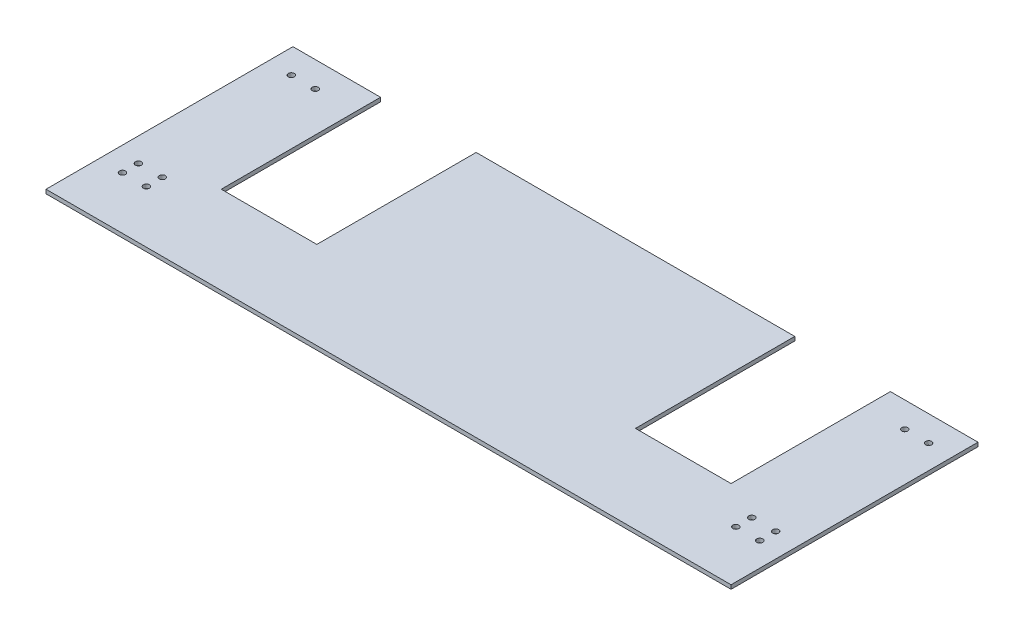
SolidWorks part; units mm, degrees
ref_plane "Front Plane" through (0, 0, 0) normal (0, 0, 1) x (1, 0, 0)
ref_plane "Top Plane" through (0, 0, 0) normal (0, 1, 0) x (1, 0, 0)
ref_plane "Right Plane" through (0, 0, 0) normal (1, 0, 0) x (0, 0, -1)
sketch "Sketch1" plane through (0, 0, 0) normal (0, 0, 1) x (1, 0, 0)
  line L1 (-273.05, -1.5875) -> (273.05, -1.5875)
  line L2 (-273.05, -1.5875) -> (-273.05, 1.5875)
  line L3 (-273.05, 1.5875) -> (273.05, 1.5875)
  line L4 (273.05, -1.5875) -> (273.05, 1.5875)
  line L5 (-273.05, -1.5875) -> (273.05, 1.5875) construction
  line L6 (-273.05, 1.5875) -> (273.05, -1.5875) construction
  point P0 (0, 0)
  dimension "D1" = 3.175
  dimension "D2" = 546.1
extrude "Boss-Extrude1" add sketch "Sketch1" along normal blind 184.15
sketch "Sketch2" plane through (0, 1.5875, 0) normal (0, 1, 0) x (1, 0, 0)
  line L4 (273.05, 0) -> (-273.05, 0) construction
  line L5 (-273.05, -184.15) -> (-273.05, 0) construction
  line L6 (0, 0) -> (0, -184.15)
  line L7 (273.05, -184.15) -> (-273.05, -184.15) construction
  line L11 (-273.05, -68.58) -> (273.05, -68.58)
  line L15 (273.05, -184.15) -> (273.05, 0) construction
  line L19 (-254, -129.54) -> (-251.587, -129.54) construction
  line L20 (-254, -129.54) -> (-254, -127.762)
  line L21 (-254, -127.762) -> (-254, -129.54)
  line L22 (-255.778, -129.54) -> (-254, -129.54)
  line L23 (-254, -131.318) -> (-254, -129.54)
  line L24 (-254, -129.54) -> (-254, -131.318)
  line L34 (-232.537, -129.54) -> (254, -129.54)
  circle A18 centre (-234.95, -129.54) radius 2.413
  circle A20 centre (-254, -129.54) radius 2.413
  circle A27 centre (-254, -7.62) radius 2.413
  circle A28 centre (-234.95, -7.62) radius 2.413
  circle A29 centre (254, -7.62) radius 2.413
  circle A30 centre (234.95, -7.62) radius 2.413
  circle A31 centre (254, -129.54) radius 2.413
  circle A32 centre (234.95, -129.54) radius 2.413
  dimension "D2" = 4.826
  dimension "D5" = 68.58
  dimension "D13" = 19.05
  dimension "D14" = 4.826
  dimension "D17" = 19.05
extrude "Cut-Extrude2" cut sketch "Sketch2" against normal through all contours A27 | A28 | A31 | A29 | A18 | A20 | A32 | A30 region at (254, 1.5875, 127.1952) region at (-254, 1.5875, 7.62) region at (-234.95, 1.5875, 7.62)
sketch "Sketch3" plane through (0, 1.5875, 0) normal (0, 1, 0) x (1, 0, 0)
  line L0 (-273.05, -184.15) -> (-273.05, 0) construction
  line L1 (-273.05, -42.9615) -> (273.05, -42.9615)
  line L2 (-273.05, -42.9615) -> (-273.05, -55.6615)
  line L3 (-273.05, -55.6615) -> (273.05, -55.6615)
  line L4 (273.05, -42.9615) -> (273.05, -55.6615)
  line L5 (273.05, -184.15) -> (273.05, 0) construction
  dimension "D1" = 12.7
sketch "Sketch5" plane through (0, 0, 0) normal (0, 0, -1) x (-1, 0, 0)
  line L1 (-273.05, 1.5875) -> (273.05, 1.5875)
  line L2 (-273.05, 1.5875) -> (-273.05, -1.5875)
  line L3 (-273.05, -1.5875) -> (273.05, -1.5875)
  line L4 (273.05, 1.5875) -> (273.05, -1.5875)
extrude "Boss-Extrude2" add sketch "Sketch5" along normal blind 12.7 contours L2 L1 L4 L3
sketch "Sketch6" plane through (0, 1.5875, 0) normal (0, 1, 0) x (1, 0, 0)
  line L0 (273.05, 12.7) -> (-273.05, 12.7) construction
  line L1 (-203.2, 12.7) -> (-127, 12.7)
  line L2 (-203.2, 12.7) -> (-203.2, -114.3)
  line L3 (-203.2, -114.3) -> (-127, -114.3)
  line L4 (-127, 12.7) -> (-127, -114.3)
  line L5 (0, 12.7) -> (0, -184.15)
  line L6 (127, 12.7) -> (203.2, 12.7)
  line L7 (127, 12.7) -> (127, -114.3)
  line L8 (127, -114.3) -> (203.2, -114.3)
  line L9 (203.2, 12.7) -> (203.2, -114.3)
  line L10 (273.05, -184.15) -> (-273.05, -184.15) construction
  line M12 (273.05, 12.7) -> (-273.05, 12.7)
  dimension "D1" = 127
  dimension "D2" = 76.2
  dimension "D3" = 127
  dimension "D4" = 127
  dimension "D5" = 76.2
  dimension "D6" = 127
extrude "Cut-Extrude4" cut sketch "Sketch6" against normal through all contours L4 L2 L3 M12 | L9 L7 L8 M12 region at (165.1, 1.5875, 50.8) region at (-165.1, 1.5875, 50.8)
sketch "Sketch7" plane through (0, 1.5875, 0) normal (0, 1, 0) x (1, 0, 0)
  line L0 (-273.05, -184.15) -> (-273.05, 12.7) construction
  line L1 (273.05, -184.15) -> (-273.05, -184.15) construction
  line L2 (0, -6.7677) -> (0, -184.15)
  circle A0 centre (-254, -142.24) radius 2.413
  circle A1 centre (-234.95, -142.24) radius 2.413
  circle A2 centre (234.95, -142.24) radius 2.413
  circle A3 centre (254, -142.24) radius 2.413
  point P14 (0, 0)
  dimension "D1" = 4.826
  dimension "D2" = 4.826
  dimension "D3" = 19.05
  dimension "D4" = 41.91
  dimension "D5" = 41.91
  dimension "D6" = 19.05
extrude "Cut-Extrude5" cut sketch "Sketch7" against normal through all contours A0 | A1 | A3 | A2 region at (-254, 1.5875, 142.24) region at (-234.95, 1.5875, 142.24) region at (234.95, 1.5875, 142.24) region at (254, 1.5875, 142.24)
